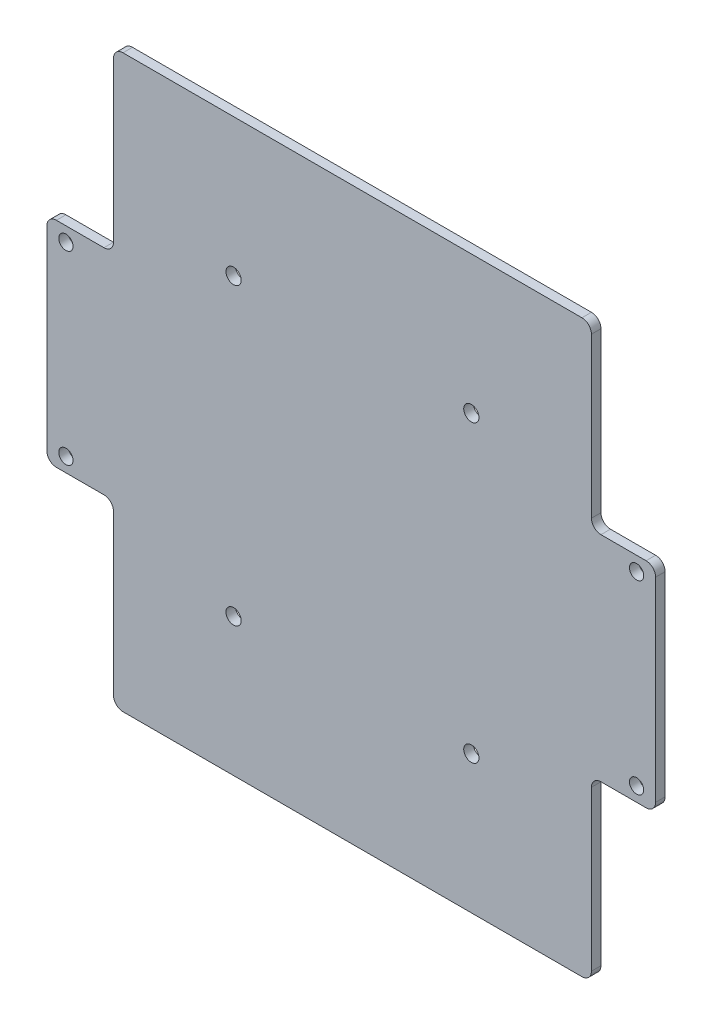
SolidWorks part; units mm, degrees
material "Thornel Mat VMA"
ref_plane "前视基准面" through (0, 0, 0) normal (0, 0, 1) x (1, 0, 0)
ref_plane "上视基准面" through (0, 0, 0) normal (0, 1, 0) x (1, 0, 0)
ref_plane "右视基准面" through (0, 0, 0) normal (1, 0, 0) x (0, 0, -1)
sketch "草图1" plane through (0, 0, 0) normal (0, 0, 1) x (1, 0, 0)
  line L1 (0, 0) -> (60, 0)
  line L2 (0, 0) -> (0, 70)
  line L3 (0, 70) -> (60, 70)
  line L4 (60, 0) -> (60, 70)
  line L5 (5, 66) -> (55, 66)
  line L6 (5, 66) -> (5, 4)
  line L7 (5, 4) -> (55, 4)
  line L8 (55, 66) -> (55, 4)
  circle A0 centre (5, 66) radius 1.5
  circle A1 centre (55, 66) radius 1.5
  circle A2 centre (5, 4) radius 1.5
  circle A3 centre (55, 4) radius 1.5
  dimension "D7" = 3
  dimension "D1" = 70
  dimension "D2" = 60
  dimension "D3" = 50
  dimension "D4" = 62
  dimension "D5" = 4
  dimension "D6" = 5
extrude "凸台-拉伸1" add sketch "草图1" along normal blind 2 contours A3 L8 A1 L5 A0 L6 A2 L7 | L1 L4 L3 L2 A3 L7 A2 L6 A0 L5 A1 L8 region at (0.922, 35, 0) region at (30, 35, 0)
sketch "草图2" plane through (0, 0, 2) normal (0, 0, 1) x (1, 0, 0)
  line L0 (60, 0) -> (60, 70) construction
  line L1 (60, 57.5) -> (94, 57.5)
  line L2 (60, 57.5) -> (60, 12.5)
  line L3 (60, 12.5) -> (94, 12.5)
  line L4 (94, 57.5) -> (94, 12.5)
  line L5 (0, 0) -> (60, 0) construction
  dimension "D1" = 34
  dimension "D2" = 45
  dimension "D3" = 12.5
extrude "凸台-拉伸2" add sketch "草图2" against normal blind 2
ref_plane "基准面1" through (30, 0, 0) normal (1, 0, 0) x (0, 0, -1)
mirror "镜向1" about plane through (30, 0, 0) normal (1, 0, 0) of "凸台-拉伸2"
sketch "草图3" plane through (0, 0, 2) normal (0, 0, 1) x (1, 0, 0)
  line L0 (94, 12.5) -> (94, 57.5) construction
  line L1 (-30, 54.5) -> (90, 54.5)
  line L2 (-30, 54.5) -> (-30, 15.5)
  line L3 (-30, 15.5) -> (90, 15.5)
  line L4 (90, 54.5) -> (90, 15.5)
  line L5 (94, 57.5) -> (60, 57.5) construction
  circle A0 centre (90, 54.5) radius 1.5
  circle A1 centre (90, 15.5) radius 1.5
  circle A2 centre (-30, 54.5) radius 1.5
  circle A3 centre (-30, 15.5) radius 1.5
  dimension "D5" = 3
  dimension "D1" = 120
  dimension "D2" = 4
  dimension "D3" = 39
  dimension "D4" = 3
extrude "切除-拉伸1" cut sketch "草图3" against normal through all and the other way blind 1 contours L1 A2 L2 | L2 A2 L1 | L2 A3 L3 | L3 A3 L2 | L1 A0 L4 | L4 A0 L1 | L4 A1 L3 | L3 A1 L4 region at (-30.2122, 54.7122, 2) region at (-29.3634, 53.8634, 2) region at (90.2122, 54.7122, 2) region at (89.3634, 53.8634, 2) region at (-29.3634, 16.1366, 2) region at (-30.2122, 15.2878, 2) region at (90.2122, 15.2878, 2) region at (89.3634, 16.1366, 2)
fillet "圆角1" radius 2 12 edges at (60, 70, 1) (60, 57.5, 1) (94, 57.5, 1) (94, 12.5, 1) (60, 12.5, 1) (60, 0, 1) (0, 0, 1) (0, 12.5, 1) (-34, 12.5, 1) (0, 70, 1) (0, 57.5, 1) (-34, 57.5, 1)
sketch "草图4" plane through (0, 0, 2) normal (0, 0, 1) x (1, 0, 0)
  line L0 (11, 55) -> (11, 15) construction
  line L1 (15, 55) -> (15, 15)
  line L2 (7, 55) -> (7, 15)
  line L3 (-34, 14.5) -> (-34, 55.5) construction
  arc A0 (15, 55) -> (7, 55) centre (11, 55) ccw
  arc A1 (7, 15) -> (15, 15) centre (11, 15) ccw
  point P2 (11, 35)
  point P9 (-34, 35)
  dimension "D1" = 45
  dimension "D2" = 8
  dimension "D3" = 40
extrude "切除-拉伸2" cut sketch "草图4" against normal through all
pattern_linear "阵列(线性)1" count 4 spacing 14 along (1, 0, 0) of "切除-拉伸2"
sketch "草图6" plane through (0, 0, 2) normal (0, 0, 1) x (1, 0, 0)
  line L0 (-34, 14.5) -> (-34, 55.5) construction
  line L1 (-20, 95) -> (-20, -25)
  line L2 (-20, -25) -> (80.508, -25)
  line L3 (80.508, -25) -> (80.508, 95)
  line L4 (80.508, 95) -> (-20, 95)
  line L6 (94, 14.5) -> (94, 55.5) construction
  line L8 (30, 0) -> (30, 70) construction
  line L9 (2, 0) -> (58, 0) construction
  line L10 (2, 70) -> (58, 70) construction
  line L11 (94, 35) -> (-34, 35) construction
  dimension "D1" = 120
  dimension "D2" = 60
  dimension "D3" = 50
extrude "凸台-拉伸3" add sketch "草图6" against normal blind 2
sketch "草图7" plane through (0, 0, 2) normal (0, 0, 1) x (1, 0, 0)
  line L0 (30.254, 95) -> (30.254, -25) construction
  line L1 (55.254, 4) -> (5.254, 4)
  line L2 (55.254, 4) -> (55.254, 66)
  line L3 (55.254, 66) -> (5.254, 66)
  line L4 (5.254, 4) -> (5.254, 66)
  line L5 (55.254, 4) -> (5.254, 66) construction
  line L6 (55.254, 66) -> (5.254, 4) construction
  line L7 (80.508, 95) -> (-20, 95) construction
  line L8 (-20, -25) -> (80.508, -25) construction
  line L9 (-34, 35) -> (94, 35) construction
  line L10 (-34, 14.5) -> (-34, 55.5) construction
  line L11 (94, 14.5) -> (94, 55.5) construction
  circle A0 centre (5.254, 66) radius 1.6
  circle A1 centre (55.254, 66) radius 1.6
  circle A2 centre (55.254, 4) radius 1.6
  circle A3 centre (5.254, 4) radius 1.6
  point P0 (30.254, 35)
  point P18 (30.254, 35)
  dimension "D3" = 3.2
  dimension "D1" = 50
  dimension "D2" = 62
extrude "切除-拉伸3" cut sketch "草图7" against normal blind 3 contours L4 A0 L3 | L3 A0 L4 | L3 A1 L2 | L2 A1 L3 | L1 A3 L4 | L4 A3 L1 | L2 A2 L1 | L1 A2 L2 region at (5.0276, 3.7736, 2) region at (5.9331, 4.6791, 2) region at (54.5749, 4.6791, 2) region at (55.4803, 3.7736, 2) region at (5.0276, 66.2264, 2) region at (5.9331, 65.3209, 2) region at (54.5749, 65.3209, 2) region at (55.4803, 66.2264, 2)
fillet "圆角2" radius 2 8 edges at (-20, 57.5, 1) (-20, 95, 1) (80.508, 95, 1) (80.508, 57.5, 1) (80.508, 12.5, 1) (80.508, -25, 1) (-20, -25, 1) (-20, 12.5, 1)
